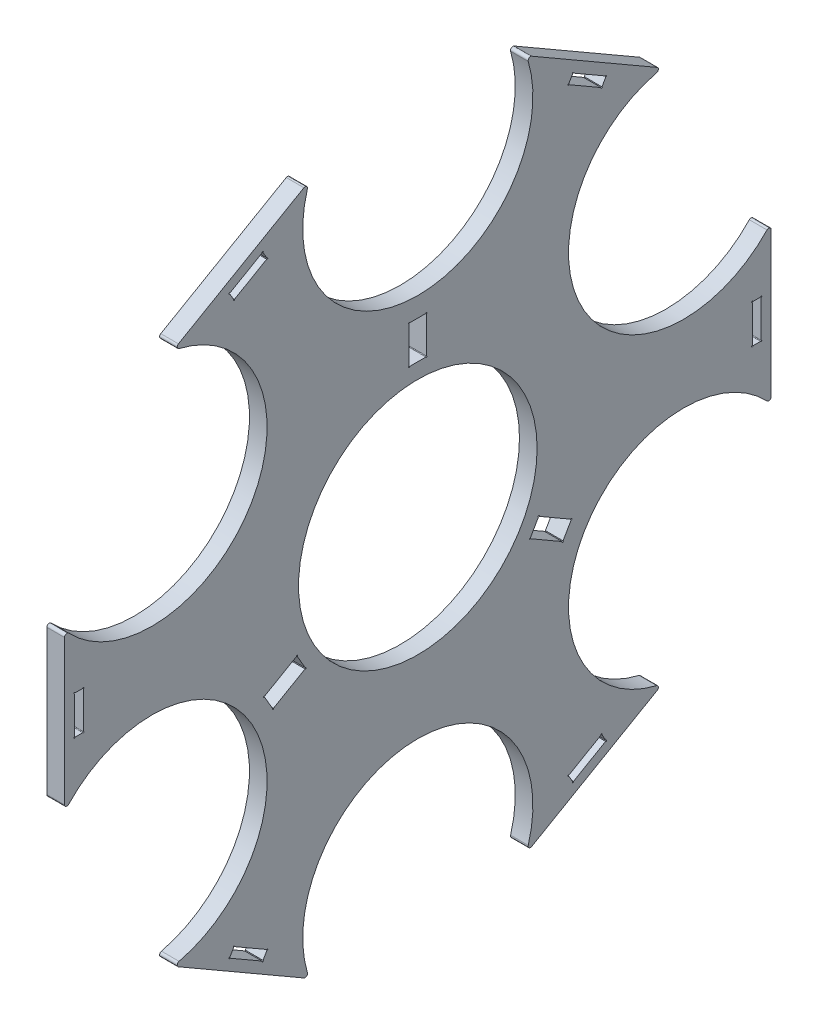
SolidWorks part; units mm, degrees
ref_plane "Front Plane" through (0, 0, 0) normal (0, 0, 1) x (1, 0, 0)
ref_plane "Top Plane" through (0, 0, 0) normal (0, 1, 0) x (1, 0, 0)
ref_plane "Right Plane" through (0, 0, 0) normal (1, 0, 0) x (0, 0, -1)
sketch "Sketch2" plane through (0, 0, 0) normal (1, 0, 0) x (0, 0, -1)
  line L0 (35.921, 114.3) -> (-35.921, 114.3) construction
  line L1 (81.0262, 88.2585) -> (35.921, 114.3)
  line L2 (116.9472, -26.0415) -> (116.9472, 26.0415)
  line L3 (35.921, -114.3) -> (81.0262, -88.2585)
  line L4 (-81.0262, -88.2585) -> (-35.921, -114.3)
  line L5 (-116.9472, 26.0415) -> (-116.9472, -26.0415)
  line L6 (-35.921, 114.3) -> (-81.0262, 88.2585)
  circle A0 centre (0, 0) radius 101.6 construction
  arc A1 (-35.921, 114.3) -> (35.921, 114.3) centre (0, 101.6) ccw
  arc A2 (81.0262, 88.2585) -> (116.9472, 26.0415) centre (87.9882, 50.8) ccw
  arc A3 (116.9472, -26.0415) -> (81.0262, -88.2585) centre (87.9882, -50.8) ccw
  arc A4 (35.921, -114.3) -> (-35.921, -114.3) centre (0, -101.6) ccw
  arc A5 (-81.0262, -88.2585) -> (-116.9472, -26.0415) centre (-87.9882, -50.8) ccw
  arc A6 (-116.9472, 26.0415) -> (-81.0262, 88.2585) centre (-87.9882, 50.8) ccw
  circle A7 centre (0, 0) radius 39.4875
  point P23 (0, 0)
  point P34 (0, 0)
  dimension "D1" = 203.2
  dimension "D2" = 114.3
  dimension "D3" = 76.2
  dimension "D6" = 78.9749
  dimension "D4" = 6
  dimension "D5" = 6
extrude "Boss-Extrude1" add sketch "Sketch2" along normal blind 5.842 contours A6 L5 A5 L4 A4 L3 A3 L2 A2 L1 A1 L6 region at (0, 30.1147, -52.1602)
fillet "Fillet1" radius 0.7937 12 edges at (2.921, -114.3, 35.921) (2.921, -114.3, -35.921) (2.921, -88.2585, -81.0262) (2.921, -26.0415, -116.9472) (2.921, 88.2585, -81.0262) (2.921, 26.0415, -116.9472) (2.921, -88.2585, 81.0262) (2.921, -26.0415, 116.9472) (2.921, 26.0415, 116.9472) (2.921, 88.2585, 81.0262) (2.921, 114.3, -35.921) (2.921, 114.3, 35.921)
sketch "Sketch3" plane through (5.842, 0, 0) normal (1, 0, 0) x (0, 0, -1)
  line L0 (0, 0) -> (0, 50.8) construction
  line L2 (6.1516, 53.721) -> (-6.1516, 53.721)
  line L3 (6.35, 53.5226) -> (6.35, 48.0774)
  line L4 (6.1516, 47.879) -> (-6.1516, 47.879)
  line L5 (-6.35, 53.5226) -> (-6.35, 48.0774)
  line L6 (6.35, 53.721) -> (-6.35, 47.879) construction
  line L7 (6.35, 47.879) -> (-6.35, 53.721) construction
  arc A0 (-6.1516, 53.721) -> (-6.35, 53.5226) centre (-6.35, 53.721) ccw
  arc A1 (-6.35, 48.0774) -> (-6.1516, 47.879) centre (-6.35, 47.879) ccw
  arc A2 (6.1516, 47.879) -> (6.35, 48.0774) centre (6.35, 47.879) ccw
  arc A3 (6.35, 53.5226) -> (6.1516, 53.721) centre (6.35, 53.721) ccw
  dimension "D4" = 0.3969
  dimension "D5" = 0.3969
  dimension "D6" = 0.3969
  dimension "D7" = 0.3969
  dimension "D1" = 50.8
  dimension "D2" = 12.7
  dimension "D3" = 5.842
extrude "Cut-Extrude2" [suppressed] cut sketch "Sketch3" against normal through all
pattern_circular "CirPattern1" [suppressed] count 3 every 120 of bodies 112
sketch "Sketch4" plane through (5.842, 0, 0) normal (1, 0, 0) x (0, 0, -1)
  line L0 (47.9712, -31.0114) -> (50.8422, -26.0386)
  line L1 (2.871, 57.05) -> (-2.871, 57.05)
  line L2 (2.871, 57.05) -> (2.871, 44.55)
  line L3 (2.871, 44.55) -> (-2.871, 44.55)
  line L4 (-2.871, 57.05) -> (-2.871, 44.55)
  line L5 (2.871, 57.05) -> (-2.871, 44.55) construction
  line L6 (2.871, 44.55) -> (-2.871, 57.05) construction
  line L7 (47.9712, -31.0114) -> (37.1459, -24.7614)
  line L8 (37.1459, -24.7614) -> (40.0169, -19.7886)
  line L9 (50.8422, -26.0386) -> (40.0169, -19.7886)
  line L10 (47.9712, -31.0114) -> (40.0169, -19.7886) construction
  line L11 (37.1459, -24.7614) -> (50.8422, -26.0386) construction
  line L12 (-50.8422, -26.0386) -> (-47.9712, -31.0114)
  line L13 (-50.8422, -26.0386) -> (-40.0169, -19.7886)
  line L14 (-40.0169, -19.7886) -> (-37.1459, -24.7614)
  line L15 (-47.9712, -31.0114) -> (-37.1459, -24.7614)
  line L16 (-50.8422, -26.0386) -> (-37.1459, -24.7614) construction
  line L17 (-40.0169, -19.7886) -> (-47.9712, -31.0114) construction
  circle A0 centre (0, 0) radius 50.8 construction
  point P3 (0, 50.8)
  point P10 (43.9941, -25.4)
  point P15 (-43.9941, -25.4)
  point P20 (0, 0)
  dimension "D1" = 101.6
  dimension "D2" = 12.5
  dimension "D3" = 5.742
  dimension "D4" = 3
extrude "Cut-Extrude3" cut sketch "Sketch4" against normal through all
sketch "Sketch5" plane through (5.842, 0, 0) normal (1, 0, 0) x (0, 0, -1)
  line L0 (-2.871, 50.8) -> (2.871, 50.8) construction
  line L1 (-2.871, 57.05) -> (-2.871, 44.55) construction
  line L2 (2.871, 44.55) -> (2.871, 57.05) construction
  line L3 (45.4296, -22.9136) -> (42.5586, -27.8864) construction
  line L4 (-42.5586, -27.8864) -> (-45.4296, -22.9136) construction
  circle A0 centre (2.871, 57.05) radius 0.1984
  circle A1 centre (-2.871, 57.05) radius 0.1984
  circle A2 centre (-2.871, 44.55) radius 0.1984
  circle A3 centre (2.871, 44.55) radius 0.1984
  circle A4 centre (47.9712, -31.0114) radius 0.1984
  circle A5 centre (50.8422, -26.0386) radius 0.1984
  circle A6 centre (40.0169, -19.7886) radius 0.1984
  circle A7 centre (37.1459, -24.7614) radius 0.1984
  circle A8 centre (-50.8422, -26.0386) radius 0.1984
  circle A9 centre (-47.9712, -31.0114) radius 0.1984
  circle A10 centre (-37.1459, -24.7614) radius 0.1984
  circle A11 centre (-40.0169, -19.7886) radius 0.1984
  point P38 (0, 0)
  dimension "D1" = 0.3969
  dimension "D2" = 0.3969
  dimension "D3" = 3
extrude "Cut-Extrude4" cut sketch "Sketch5" against normal through all
sketch "Sketch6" plane through (5.842, 0, 0) normal (1, 0, 0) x (0, 0, -1)
  line L0 (-58.4736, 101.2793) -> (0, 0) construction
  line L1 (-37.7084, 113.2681) -> (-79.2388, 89.2905) construction
  line L2 (-32.1468, 110.9798) -> (-80.0379, 83.3298) construction
  line L3 (-49.8493, 99.0416) -> (-60.8479, 92.6916)
  line L4 (-49.8493, 99.0416) -> (-51.3368, 101.618)
  line L5 (-60.8479, 92.6916) -> (-62.3354, 95.268)
  line L6 (-51.3368, 101.618) -> (-62.3354, 95.268)
  line L7 (-49.8493, 99.0416) -> (-62.3354, 95.268) construction
  line L8 (-60.8479, 92.6916) -> (-51.3368, 101.618) construction
  line L9 (60.8479, 92.6916) -> (49.8493, 99.0416)
  line L10 (60.8479, 92.6916) -> (62.3354, 95.268)
  line L11 (49.8493, 99.0416) -> (51.3368, 101.618)
  line L12 (62.3354, 95.268) -> (51.3368, 101.618)
  line L13 (58.4736, 101.2793) -> (0, 0) construction
  line L14 (80.0379, 83.3298) -> (32.1468, 110.9798) construction
  line L15 (60.8479, 92.6916) -> (51.3368, 101.618) construction
  line L16 (49.8493, 99.0416) -> (62.3354, 95.268) construction
  line L17 (110.6972, -6.35) -> (110.6972, 6.35)
  line L18 (110.6972, -6.35) -> (113.6722, -6.35)
  line L19 (110.6972, 6.35) -> (113.6722, 6.35)
  line L20 (113.6722, -6.35) -> (113.6722, 6.35)
  line L21 (116.9472, 0) -> (0, 0) construction
  line L22 (112.1847, -27.65) -> (112.1847, 27.65) construction
  line L23 (110.6972, -6.35) -> (113.6722, 6.35) construction
  line L24 (110.6972, 6.35) -> (113.6722, -6.35) construction
  line L25 (49.8493, -99.0416) -> (60.8479, -92.6916)
  line L26 (49.8493, -99.0416) -> (51.3368, -101.618)
  line L27 (60.8479, -92.6916) -> (62.3354, -95.268)
  line L28 (51.3368, -101.618) -> (62.3354, -95.268)
  line L29 (58.4736, -101.2793) -> (0, 0) construction
  line L30 (32.1468, -110.9798) -> (80.0379, -83.3298) construction
  line L31 (49.8493, -99.0416) -> (62.3354, -95.268) construction
  line L32 (60.8479, -92.6916) -> (51.3368, -101.618) construction
  line L33 (-60.8479, -92.6916) -> (-49.8493, -99.0416)
  line L34 (-60.8479, -92.6916) -> (-62.3354, -95.268)
  line L35 (-49.8493, -99.0416) -> (-51.3368, -101.618)
  line L36 (-62.3354, -95.268) -> (-51.3368, -101.618)
  line L37 (-58.4736, -101.2793) -> (0, 0) construction
  line L38 (-80.0379, -83.3298) -> (-32.1468, -110.9798) construction
  line L39 (-60.8479, -92.6916) -> (-51.3368, -101.618) construction
  line L40 (-49.8493, -99.0416) -> (-62.3354, -95.268) construction
  line L41 (-110.6972, 6.35) -> (-110.6972, -6.35)
  line L42 (-110.6972, 6.35) -> (-113.6722, 6.35)
  line L43 (-110.6972, -6.35) -> (-113.6722, -6.35)
  line L44 (-113.6722, 6.35) -> (-113.6722, -6.35)
  line L45 (-116.9472, 0) -> (0, 0) construction
  line L46 (-112.1847, 27.65) -> (-112.1847, -27.65) construction
  line L47 (-110.6972, 6.35) -> (-113.6722, -6.35) construction
  line L48 (-110.6972, -6.35) -> (-113.6722, 6.35) construction
  point P8 (-56.0924, 97.1548)
  point P9 (-56.0924, 97.1548)
  point P18 (56.0924, 97.1548)
  point P19 (56.0924, 97.1548)
  point P27 (112.1847, 0)
  point P28 (112.1847, 0)
  point P36 (56.0924, -97.1548)
  point P37 (56.0924, -97.1548)
  point P45 (-56.0924, -97.1548)
  point P46 (-56.0924, -97.1548)
  point P54 (-112.1847, 0)
  point P55 (-112.1847, 0)
  point P60 (0, 0)
  dimension "D1" = 4.7625
  dimension "D2" = 2.975
  dimension "D3" = 12.7
  dimension "D4" = 6
extrude "Cut-Extrude5" cut sketch "Sketch6" against normal through all
sketch "Sketch7" plane through (5.842, 0, 0) normal (1, 0, 0) x (0, 0, -1)
  line L0 (-62.3354, 95.268) -> (-60.8479, 92.6916) construction
  circle A0 centre (-51.3368, 101.618) radius 0.1984
  circle A1 centre (-49.8493, 99.0416) radius 0.1984
  circle A2 centre (-60.8479, 92.6916) radius 0.1984
  circle A3 centre (-62.3354, 95.268) radius 0.1984
  circle A4 centre (62.3354, 95.268) radius 0.1984
  circle A5 centre (60.8479, 92.6916) radius 0.1984
  circle A6 centre (49.8493, 99.0416) radius 0.1984
  circle A7 centre (51.3368, 101.618) radius 0.1984
  circle A8 centre (113.6722, -6.35) radius 0.1984
  circle A9 centre (110.6972, -6.35) radius 0.1984
  circle A10 centre (110.6972, 6.35) radius 0.1984
  circle A11 centre (113.6722, 6.35) radius 0.1984
  circle A12 centre (51.3368, -101.618) radius 0.1984
  circle A13 centre (49.8493, -99.0416) radius 0.1984
  circle A14 centre (60.8479, -92.6916) radius 0.1984
  circle A15 centre (62.3354, -95.268) radius 0.1984
  circle A16 centre (-62.3354, -95.268) radius 0.1984
  circle A17 centre (-60.8479, -92.6916) radius 0.1984
  circle A18 centre (-49.8493, -99.0416) radius 0.1984
  circle A19 centre (-51.3368, -101.618) radius 0.1984
  circle A20 centre (-113.6722, 6.35) radius 0.1984
  circle A21 centre (-110.6972, 6.35) radius 0.1984
  circle A22 centre (-110.6972, -6.35) radius 0.1984
  circle A23 centre (-113.6722, -6.35) radius 0.1984
  point P55 (0, 0)
  dimension "D1" = 0.3969
  dimension "D2" = 0.3969
  dimension "D3" = 0.3969
  dimension "D4" = 0.3969
  dimension "D5" = 6
extrude "Cut-Extrude6" cut sketch "Sketch7" against normal through all
